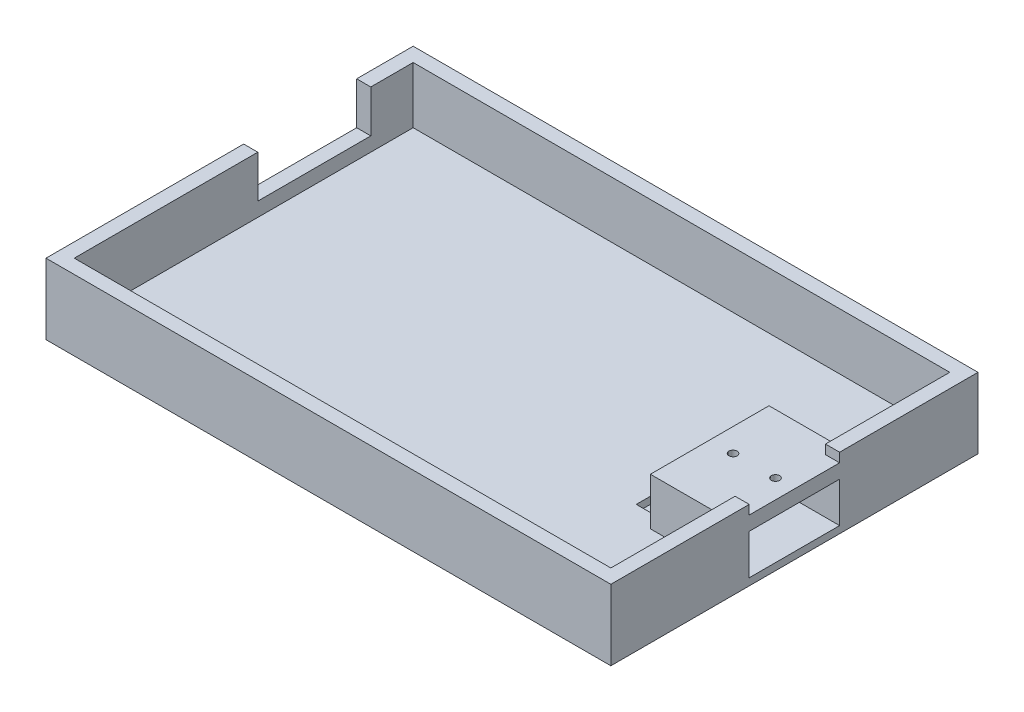
SolidWorks part; units mm, degrees
ref_plane "Front Plane" through (0, 0, 0) normal (0, 0, 1) x (1, 0, 0)
ref_plane "Top Plane" through (0, 0, 0) normal (0, 1, 0) x (1, 0, 0)
ref_plane "Right Plane" through (0, 0, 0) normal (1, 0, 0) x (0, 0, -1)
sketch "Sketch1" plane through (0, 0, 0) normal (0, 1, 0) x (1, 0, 0)
  line L1 (-127, -82.55) -> (127, -82.55)
  line L2 (-127, -82.55) -> (-127, 82.55)
  line L3 (-127, 82.55) -> (127, 82.55)
  line L4 (127, -82.55) -> (127, 82.55)
  line L5 (-127, -82.55) -> (127, 82.55) construction
  line L6 (-127, 82.55) -> (127, -82.55) construction
  point P0 (0, 0)
  dimension "D1" = 254
  dimension "D2" = 165.1
extrude "Boss-Extrude1" add sketch "Sketch1" along normal blind 6.35
sketch "Sketch2" plane through (0, 6.35, 0) normal (0, 1, 0) x (1, 0, 0)
  line L0 (127, -82.55) -> (127, 82.55) construction
  line L1 (-127, 82.55) -> (127, 82.55)
  line L2 (-127, 82.55) -> (-127, 76.2)
  line L3 (-127, 76.2) -> (127, 76.2)
  line L4 (127, 82.55) -> (127, 76.2)
  line L5 (-127, 82.55) -> (-127, -82.55) construction
  line L6 (127, -82.55) -> (-127, -82.55)
  line L7 (127, -82.55) -> (127, -76.2)
  line L8 (127, -76.2) -> (-127, -76.2)
  line L9 (-127, -82.55) -> (-127, -76.2)
  line L11 (-127, -76.2) -> (-120.65, -76.2)
  line L12 (-127, -76.2) -> (-127, 76.2)
  line L13 (-127, 76.2) -> (-120.65, 76.2)
  line L14 (-120.65, -76.2) -> (-120.65, 76.2)
  line L15 (127, 76.2) -> (120.65, 76.2)
  line L16 (127, 76.2) -> (127, -76.2)
  line L17 (127, -76.2) -> (120.65, -76.2)
  line L18 (120.65, 76.2) -> (120.65, -76.2)
  line M13 (127, -82.55) -> (127, 82.55)
  line M14 (127, 82.55) -> (-127, 82.55)
  line M15 (-127, 82.55) -> (-127, -82.55)
  line M16 (-127, -82.55) -> (127, -82.55)
  dimension "D1" = 6.35
extrude "Boss-Extrude2" add sketch "Sketch2" along normal blind 25.4 contours L8 L14 L3 M15 | L3 M15 M13 M14 | L3 L18 L8 M13 | L8 M13 M15 M16 region at (0, 6.35, -79.375) region at (-123.825, 6.35, 0) region at (123.825, 6.35, 0) region at (0, 6.35, 79.375)
sketch "Sketch3" plane through (0, 31.75, 0) normal (0, 1, 0) x (1, 0, 0)
  line L0 (120.65, 76.2) -> (120.65, -76.2) construction
  line L1 (120.65, 20.32) -> (127, 20.32)
  line L2 (120.65, 20.32) -> (120.65, -20.32)
  line L3 (120.65, -20.32) -> (127, -20.32)
  line L4 (127, 20.32) -> (127, -20.32)
  line L5 (127, -82.55) -> (127, 82.55) construction
  point P8 (120.65, 0)
  dimension "D1" = 40.64
extrude "Cut-Extrude1" cut sketch "Sketch3" against normal up to surface (25.4 mm away) up to face at (0, 6.35, 0)
sketch "Sketch4" plane through (0, 6.35, 0) normal (0, 1, 0) x (1, 0, 0)
  line L0 (120.65, -20.32) -> (127, -20.32) construction
  line L1 (127, 20.32) -> (76.2, 20.32)
  line L2 (127, 20.32) -> (127, -20.32)
  line L3 (127, -20.32) -> (76.2, -20.32)
  line L4 (76.2, 20.32) -> (76.2, -20.32)
  dimension "D1" = 50.8
extrude "Cut-Extrude2" cut sketch "Sketch4" against normal blind 3.175
sketch "Sketch5" plane through (0, 6.35, 0) normal (0, 1, 0) x (1, 0, 0)
  line L1 (120.65, 20.32) -> (88.9, 20.32)
  line L2 (120.65, 20.32) -> (120.65, 26.67)
  line L3 (120.65, 26.67) -> (88.9, 26.67)
  line L4 (88.9, 20.32) -> (88.9, 26.67)
  dimension "D1" = 31.75
  dimension "D2" = 6.35
extrude "Boss-Extrude3" add sketch "Sketch5" along normal up to surface (14.913 mm away)
sketch "Sketch6" plane through (0, 21.263, 0) normal (0, 1, 0) x (1, 0, 0)
  line L1 (88.9, 26.67) -> (127, 26.67)
  line L2 (88.9, 26.67) -> (88.9, 0)
  line L3 (88.9, 0) -> (127, 0)
  line L4 (127, 26.67) -> (127, 0)
  line L5 (127, 20.32) -> (127, 82.55) construction
extrude "Boss-Extrude4" add sketch "Sketch6" along normal blind 6.35
mirror "Mirror1" about plane through (0, 0, 0) normal (0, 0, 1) of "Boss-Extrude4", "Boss-Extrude3"
sketch "Sketch7" plane through (0, 27.613, 0) normal (0, 1, 0) x (1, 0, 0)
  circle A0 centre (99.4, 0) radius 1.85 construction
  circle A1 centre (118.5, 0) radius 1.85 construction
  circle A2 centre (99.4, 0) radius 1.85
  circle A3 centre (118.5, 0) radius 1.85
extrude "Cut-Extrude3" cut sketch "Sketch7" against normal up to next
sketch "Sketch8" plane through (0, 31.75, 0) normal (0, 1, 0) x (1, 0, 0)
  line L0 (-127, 82.55) -> (-127, -82.55) construction
  line L1 (-127, 57.15) -> (-120.65, 57.15)
  line L2 (-127, 57.15) -> (-127, 6.35)
  line L3 (-127, 6.35) -> (-120.65, 6.35)
  line L4 (-120.65, 57.15) -> (-120.65, 6.35)
  line L5 (-120.65, -76.2) -> (-120.65, 76.2) construction
  line L6 (127, 82.55) -> (-127, 82.55) construction
  dimension "D1" = 50.8
  dimension "D2" = 25.4
extrude "Cut-Extrude4" cut sketch "Sketch8" against normal blind 19.05
